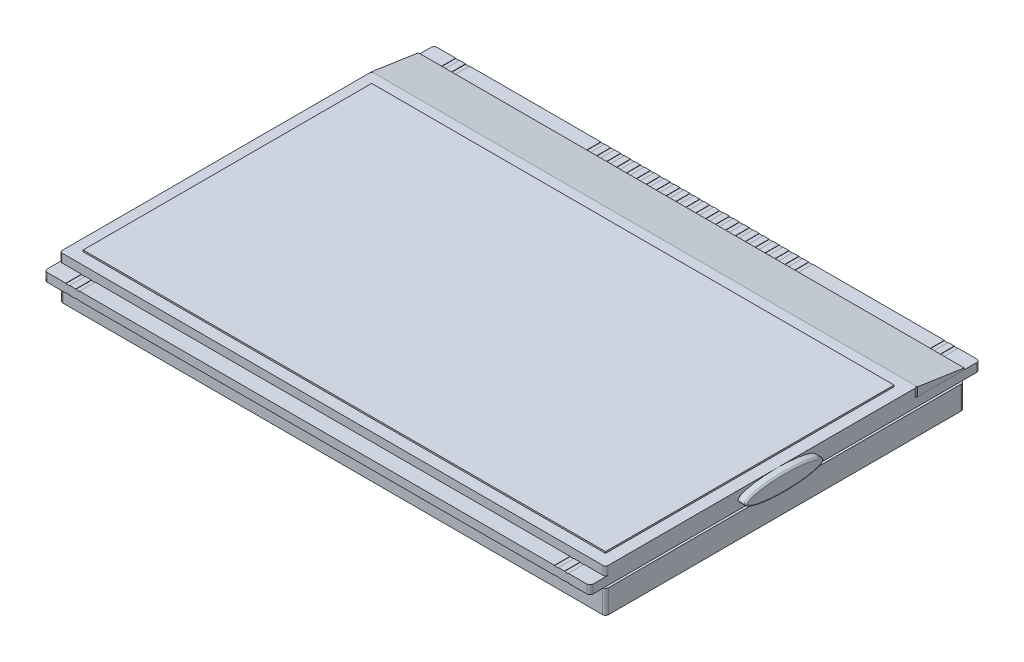
SolidWorks part; units mm, degrees
ref_plane "Front Plane" through (0, 0, 0) normal (0, 0, 1) x (1, 0, 0)
ref_plane "Top Plane" through (0, 0, 0) normal (0, 1, 0) x (1, 0, 0)
ref_plane "Right Plane" through (0, 0, 0) normal (1, 0, 0) x (0, 0, -1)
sketch "Sketch2" plane through (0, 0, 0) normal (0, 1, 0) x (1, 0, 0)
  line L0 (0, 27.3735) -> (0, -35) construction
  line L1 (-35, 27.0253) -> (35, 27.0253)
  line L2 (-35, 27.0253) -> (-35, -22.9747)
  line L3 (-35, -22.9747) -> (35, -22.9747)
  line L4 (35, 27.0253) -> (35, -22.9747)
  line L5 (-33.5, 17.5253) -> (33.5, 17.5253)
  line L6 (-33.5, 17.5253) -> (-33.5, -19.4747)
  line L7 (-33.5, -19.4747) -> (33.5, -19.4747)
  line L8 (33.5, 17.5253) -> (33.5, -19.4747)
  line L9 (-33.5, -19.4747) -> (33.5, -19.4747)
  line L10 (-35, -20.9747) -> (35, -20.9747)
  line L11 (-35, 19.0253) -> (35, 19.0253)
  point P0 (0, 0)
  point P6 (0, 0)
  dimension "D1" = 70
  dimension "D2" = 50
  dimension "D3" = 67
  dimension "D4" = 37
  dimension "D5" = 3.5
  dimension "D6" = 2
  dimension "D7" = 40
extrude "Boss-Extrude1" add sketch "Sketch2" along normal blind 1.1 contours L11 L0 L5 L8 L9 L10 L4 | L0 L11 L2 L10 L7 L6 L5 region at (17.5, 0, -18.4938) region at (-0.5315, 0, -18.2753)
extrude "Boss-Extrude2" add sketch "Sketch2<4>" along normal blind 1.3 separate body contours L0 L5 L6 L7 | L5 L0 L9 L8 region at (16.75, 0, 0.9747) region at (-16.75, 0, 0.9747)
sketch "Sketch2<4>" plane through (0, 0, 0) normal (0, 1, 0) x (1, 0, 0) same geometry as "Sketch2"
extrude "Boss-Extrude3" add sketch "Sketch2<5>" against normal blind 1.1 separate body contours L1 L0 L11 L4 | L0 L1 L2 L11 | L11 L0 L5 L8 L9 L10 L4 | L0 L11 L2 L10 L7 L6 L5 | L5 L0 L9 L8 | L0 L5 L6 L7 | L10 L0 L3 L4 | L0 L10 L2 L3 region at (17.5, 0, -23.0253) region at (-17.5, 0, -23.0253) region at (17.5, 0, -18.4938) region at (-0.5315, 0, -18.2753) region at (16.75, 0, 0.9747) region at (-16.75, 0, 0.9747) region at (-17.5, 0, 21.9747) region at (17.5, 0, 21.9747)
sketch "Sketch2<5>" plane through (0, 0, 0) normal (0, 1, 0) x (1, 0, 0) same geometry as "Sketch2"
sketch "Sketch4" plane through (0, -1.1, 0) normal (0, -1, 0) x (1, 0, 0)
  line L4 (33.5, 19.4747) -> (-33.5, 19.4747)
  line L5 (33.5, -17.5253) -> (33.5, 19.4747)
  line L6 (-33.5, -17.5253) -> (33.5, -17.5253)
  line L7 (-33.5, 19.4747) -> (-33.5, -17.5253)
  line L8 (33.5, 19.4747) -> (-33.5, 19.4747)
  line L9 (33.5, -17.5253) -> (33.5, 19.4747)
  line L10 (-33.5, -17.5253) -> (33.5, -17.5253)
  line L11 (-33.5, 19.4747) -> (-33.5, -17.5253)
  dimension "D1" = 0
extrude "Boss-Extrude4" add sketch "Sketch4" along normal blind 0.3
sketch "Sketch5" plane through (0, -1.4, 0) normal (0, -1, 0) x (1, 0, 0)
  line L0 (-45.4868, 20.9747) -> (47.8611, 20.9747) construction
  line L1 (-45.4868, -25.0253) -> (53.1096, -25.0253) construction
  line L2 (-35, -27.0253) -> (35, -27.0253) construction
  line L3 (-35, 22.9747) -> (35, 22.9747) construction
  line L4 (35, -19.0253) -> (35, -25.0253)
  line L5 (35, -25.0253) -> (-35, -25.0253)
  line L6 (-35, -25.0253) -> (-35, -19.0253)
  line L8 (-35, -19.0253) -> (35, -19.0253)
  line L9 (-35, 20.9747) -> (-35, -19.0253)
  line L10 (35, 20.9747) -> (-35, 20.9747)
  line L11 (35, -19.0253) -> (35, 20.9747)
  line L13 (-35, 20.9747) -> (-35, -19.0253)
  line L14 (35, 20.9747) -> (-35, 20.9747)
  line L15 (35, -19.0253) -> (35, 20.9747)
  dimension "D1" = 2
  dimension "D2" = 2
  dimension "D3" = 0
extrude "Boss-Extrude5" add sketch "Sketch5" along normal blind 3 separate body
fillet "Fillet1" radius 0.3 4 edges at (35, 0.55, 20.9747) (-35, 0.55, 20.9747) (-35, 0.55, -19.0253) (35, 0.55, -19.0253)
fillet "Fillet2" radius 0.4 4 edges at (35, -0.55, 22.9747) (35, -0.55, -27.0253) (-35, -0.55, -27.0253) (-35, -0.55, 22.9747)
fillet "Fillet3" radius 0.4 4 edges at (-35, -2.9, -25.0253) (35, -2.9, -25.0253) (35, -2.9, 20.9747) (-35, -2.9, 20.9747)
sketch "Sketch9" plane through (0, -4.4, 0) normal (0, -1, 0) x (1, 0, 0)
  line L0 (-34.6, -27.0253) -> (34.6, -27.0253) construction
  line L1 (25, -24.0253) -> (24, -24.0253)
  line L2 (25, -24.0253) -> (25, -23.4253)
  line L3 (25, -23.4253) -> (24, -23.4253)
  line L4 (24, -24.0253) -> (24, -23.4253)
  line L5 (25, -24.0253) -> (24, -23.4253) construction
  line L6 (25, -23.4253) -> (24, -24.0253) construction
  line L7 (-34.6, -27.0253) -> (34.6, -27.0253) construction
  line L8 (0, 0) -> (0, -35.522) construction
  line L9 (-25, -23.4253) -> (-24, -24.0253) construction
  line L10 (-25, -24.0253) -> (-24, -23.4253) construction
  line L11 (-24, -24.0253) -> (-24, -23.4253)
  line L12 (-25, -23.4253) -> (-24, -23.4253)
  line L13 (-25, -24.0253) -> (-25, -23.4253)
  line L14 (-25, -24.0253) -> (-24, -24.0253)
  point P0 (24.5, -23.7253)
  point P10 (0, -17.761)
  point P15 (-24.5, -23.7253)
  dimension "D1" = 1
  dimension "D2" = 0.6
  dimension "D3" = 3.3
  dimension "D4" = 24.5
extrude "Boss-Extrude6" add sketch "Sketch9" along normal blind 3 separate body
sketch "Sketch10" plane through (0, 0, 0) normal (0, 1, 0) x (1, 0, 0)
  line L0 (-34.7, -20.9747) -> (34.7, -20.9747) construction
  line L1 (-32.225, -20.9747) -> (-31.725, -20.9747)
  line L2 (-32.225, -20.9747) -> (-32.225, -23.4004)
  line L3 (-32.225, -23.4004) -> (-31.725, -23.4004)
  line L4 (-31.725, -20.9747) -> (-31.725, -23.4004)
  line L5 (-30.945, -20.9747) -> (-30.945, -23.4004)
  line L6 (-30.445, -20.9747) -> (-30.445, -23.4004)
  line L7 (-30.945, -20.9747) -> (-30.445, -20.9747)
  line L8 (-30.945, -23.4004) -> (-30.445, -23.4004)
  line L9 (-34.7, -20.9747) -> (-30.445, -20.9747) construction
  line L10 (-35, 26.6253) -> (-35, -22.5747) construction
  line L11 (0, -25.9549) -> (0, 4.9438) construction
  line L12 (30.445, -22.9747) -> (34.6, -22.9747)
  line L13 (30.945, -23.4004) -> (30.445, -23.4004)
  line L14 (30.945, -20.9747) -> (30.445, -20.9747)
  line L15 (30.445, -20.9747) -> (30.445, -23.4004)
  line L16 (30.945, -20.9747) -> (30.945, -23.4004)
  line L17 (31.725, -20.9747) -> (31.725, -23.4004)
  line L18 (32.225, -23.4004) -> (31.725, -23.4004)
  line L19 (32.225, -20.9747) -> (32.225, -23.4004)
  line L20 (32.225, -20.9747) -> (31.725, -20.9747)
  line L21 (-45.6387, 2.0253) -> (48.5913, 2.0253) construction
  line L22 (30.445, -20.9747) -> (34.7, -20.9747) construction
  line L23 (32.225, 25.0253) -> (31.725, 25.0253)
  line L24 (32.225, 25.0253) -> (32.225, 27.451)
  line L25 (-34.6, -22.9747) -> (34.6, -22.9747)
  line L26 (35, -22.5747) -> (35, 26.6253)
  line L27 (34.6, 27.0253) -> (-34.6, 27.0253)
  line L28 (-35, 26.6253) -> (-35, -22.5747)
  line L29 (-34.6, -22.9747) -> (-30.445, -22.9747)
  line L31 (32.225, 27.451) -> (31.725, 27.451)
  line L33 (31.725, 25.0253) -> (31.725, 27.451)
  line L34 (30.945, 25.0253) -> (30.945, 27.451)
  line L35 (30.445, 25.0253) -> (30.445, 27.451)
  line L36 (30.945, 25.0253) -> (30.445, 25.0253)
  line L37 (30.945, 27.451) -> (30.445, 27.451)
  line L38 (-30.945, 27.451) -> (-30.445, 27.451)
  line L39 (-30.945, 25.0253) -> (-30.445, 25.0253)
  line L40 (-30.445, 25.0253) -> (-30.445, 27.451)
  line L41 (-30.945, 25.0253) -> (-30.945, 27.451)
  line L42 (-31.725, 25.0253) -> (-31.725, 27.451)
  line L43 (-32.225, 27.451) -> (-31.725, 27.451)
  line L44 (-32.225, 25.0253) -> (-32.225, 27.451)
  line L45 (-32.225, 25.0253) -> (-31.725, 25.0253)
  arc A4 (34.6, -22.9747) -> (35, -22.5747) centre (34.6, -22.5747) ccw
  arc A5 (35, 26.6253) -> (34.6, 27.0253) centre (34.6, 26.6253) ccw
  arc A6 (-34.6, 27.0253) -> (-35, 26.6253) centre (-34.6, 26.6253) ccw
  arc A7 (-35, -22.5747) -> (-34.6, -22.9747) centre (-34.6, -22.5747) ccw
  arc A8 (34.6, -22.9747) -> (35, -22.5747) centre (34.6, -22.5747) ccw
  arc A9 (35, 26.6253) -> (34.6, 27.0253) centre (34.6, 26.6253) ccw
  arc A10 (-34.6, 27.0253) -> (-35, 26.6253) centre (-34.6, 26.6253) ccw
  arc A11 (-35, -22.5747) -> (-34.6, -22.9747) centre (-34.6, -22.5747) ccw
  point P4 (-31.975, -23.4004)
  line M6 (-34.6, -22.9747) -> (34.6, -22.9747)
  line M10 (34.6, 27.0253) -> (-34.6, 27.0253)
  dimension "D1" = 0.5
  dimension "D3" = 3.025
  dimension "D4" = 0
  dimension "D2" = 2
extrude "Cut-Extrude2" cut sketch "Sketch10" against normal blind 0.05 contours L19 L20 L17 M6 | L16 L14 L15 M6 | L41 L39 L40 M10 | L44 L45 L42 M10 | L33 L23 L24 M10 | L36 L34 L35 M10 | L5 L8 L6 L7 | L2 L3 L4 L1 region at (30.695, 0, 21.9747) region at (-31.975, 0, -26.0253) region at (31.975, 0, 21.9747) region at (-30.695, 0, -26.0253) region at (30.695, 0, -26.0253) region at (31.975, 0, -26.0253)
sketch "Sketch11" plane through (0, -1.1, 0) normal (0, -1, 0) x (1, 0, 0)
  line L0 (-32.225, 22.9747) -> (-31.725, 22.9747) construction
  line L1 (-31.725, 22.9747) -> (-31.725, 20.9747) construction
  line L2 (-31.725, 20.9747) -> (-32.225, 20.9747) construction
  line L3 (-32.225, 20.9747) -> (-32.225, 22.9747) construction
  line L4 (-30.945, 22.9747) -> (-30.445, 22.9747) construction
  line L5 (-30.445, 22.9747) -> (-30.445, 20.9747) construction
  line L6 (-30.445, 20.9747) -> (-30.945, 20.9747) construction
  line L7 (-30.945, 20.9747) -> (-30.945, 22.9747) construction
  line L8 (-32.225, 22.9747) -> (-31.725, 22.9747)
  line L9 (-31.725, 22.9747) -> (-31.725, 20.9747)
  line L10 (-31.725, 20.9747) -> (-32.225, 20.9747)
  line L11 (-32.225, 20.9747) -> (-32.225, 22.9747)
  line L12 (-30.945, 22.9747) -> (-30.445, 22.9747)
  line L13 (-30.445, 22.9747) -> (-30.445, 20.9747)
  line L14 (-30.445, 20.9747) -> (-30.945, 20.9747)
  line L15 (-30.945, 20.9747) -> (-30.945, 22.9747)
  line L16 (30.445, -25.0253) -> (30.945, -25.0253) construction
  line L17 (30.945, -25.0253) -> (30.945, -27.0253) construction
  line L18 (30.945, -27.0253) -> (30.445, -27.0253) construction
  line L19 (30.445, -27.0253) -> (30.445, -25.0253) construction
  line L20 (31.725, -27.0253) -> (31.725, -25.0253) construction
  line L21 (31.725, -25.0253) -> (32.225, -25.0253) construction
  line L22 (32.225, -25.0253) -> (32.225, -27.0253) construction
  line L23 (32.225, -27.0253) -> (31.725, -27.0253) construction
  line L24 (-30.945, -27.0253) -> (-30.945, -25.0253) construction
  line L25 (-30.945, -25.0253) -> (-30.445, -25.0253) construction
  line L26 (-30.445, -25.0253) -> (-30.445, -27.0253) construction
  line L27 (-30.445, -27.0253) -> (-30.945, -27.0253) construction
  line L28 (-32.225, -27.0253) -> (-32.225, -25.0253) construction
  line L29 (-32.225, -25.0253) -> (-31.725, -25.0253) construction
  line L30 (-31.725, -25.0253) -> (-31.725, -27.0253) construction
  line L31 (-31.725, -27.0253) -> (-32.225, -27.0253) construction
  line L32 (30.945, 22.9747) -> (30.945, 20.9747) construction
  line L33 (30.945, 20.9747) -> (30.445, 20.9747) construction
  line L34 (30.445, 20.9747) -> (30.445, 22.9747) construction
  line L35 (30.445, 22.9747) -> (30.945, 22.9747) construction
  line L36 (32.225, 22.9747) -> (32.225, 20.9747) construction
  line L37 (32.225, 20.9747) -> (31.725, 20.9747) construction
  line L38 (31.725, 20.9747) -> (31.725, 22.9747) construction
  line L39 (31.725, 22.9747) -> (32.225, 22.9747) construction
  line L40 (30.445, -25.0253) -> (30.945, -25.0253)
  line L41 (30.945, -25.0253) -> (30.945, -27.0253)
  line L42 (30.945, -27.0253) -> (30.445, -27.0253)
  line L43 (30.445, -27.0253) -> (30.445, -25.0253)
  line L44 (31.725, -27.0253) -> (31.725, -25.0253)
  line L45 (31.725, -25.0253) -> (32.225, -25.0253)
  line L46 (32.225, -25.0253) -> (32.225, -27.0253)
  line L47 (32.225, -27.0253) -> (31.725, -27.0253)
  line L48 (-30.945, -27.0253) -> (-30.945, -25.0253)
  line L49 (-30.945, -25.0253) -> (-30.445, -25.0253)
  line L50 (-30.445, -25.0253) -> (-30.445, -27.0253)
  line L51 (-30.445, -27.0253) -> (-30.945, -27.0253)
  line L52 (-32.225, -27.0253) -> (-32.225, -25.0253)
  line L53 (-32.225, -25.0253) -> (-31.725, -25.0253)
  line L54 (-31.725, -25.0253) -> (-31.725, -27.0253)
  line L55 (-31.725, -27.0253) -> (-32.225, -27.0253)
  line L56 (30.945, 22.9747) -> (30.945, 20.9747)
  line L57 (30.945, 20.9747) -> (30.445, 20.9747)
  line L58 (30.445, 20.9747) -> (30.445, 22.9747)
  line L59 (30.445, 22.9747) -> (30.945, 22.9747)
  line L60 (32.225, 22.9747) -> (32.225, 20.9747)
  line L61 (32.225, 20.9747) -> (31.725, 20.9747)
  line L62 (31.725, 20.9747) -> (31.725, 22.9747)
  line L63 (31.725, 22.9747) -> (32.225, 22.9747)
extrude "Cut-Extrude3" cut sketch "Sketch11" against normal blind 0.05
sketch "Sketch12" plane through (0, 0, 0) normal (0, 1, 0) x (1, 0, 0)
  line L0 (-30.445, 27.0253) -> (30.445, 27.0253) construction
  line L1 (13.555, 25.0253) -> (13.055, 25.0253)
  line L2 (13.555, 25.0253) -> (13.555, 27.0253)
  line L3 (13.555, 27.0253) -> (13.055, 27.0253)
  line L4 (13.055, 25.0253) -> (13.055, 27.0253)
  line L5 (30.945, 27.0253) -> (30.445, 27.0253) construction
  line L6 (11.785, 25.0253) -> (11.785, 27.0253)
  line L7 (12.285, 27.0253) -> (11.785, 27.0253)
  line L8 (12.285, 25.0253) -> (12.285, 27.0253)
  line L9 (12.285, 25.0253) -> (11.785, 25.0253)
  line L10 (10.515, 25.0253) -> (10.515, 27.0253)
  line L11 (11.015, 27.0253) -> (10.515, 27.0253)
  line L12 (11.015, 25.0253) -> (11.015, 27.0253)
  line L13 (11.015, 25.0253) -> (10.515, 25.0253)
  line L14 (9.245, 25.0253) -> (9.245, 27.0253)
  line L15 (9.745, 27.0253) -> (9.245, 27.0253)
  line L16 (9.745, 25.0253) -> (9.745, 27.0253)
  line L17 (9.745, 25.0253) -> (9.245, 25.0253)
  line L18 (7.975, 25.0253) -> (7.975, 27.0253)
  line L19 (8.475, 27.0253) -> (7.975, 27.0253)
  line L20 (8.475, 25.0253) -> (8.475, 27.0253)
  line L21 (8.475, 25.0253) -> (7.975, 25.0253)
  line L22 (6.705, 25.0253) -> (6.705, 27.0253)
  line L23 (7.205, 27.0253) -> (6.705, 27.0253)
  line L24 (7.205, 25.0253) -> (7.205, 27.0253)
  line L25 (7.205, 25.0253) -> (6.705, 25.0253)
  line L26 (5.435, 25.0253) -> (5.435, 27.0253)
  line L27 (5.935, 27.0253) -> (5.435, 27.0253)
  line L28 (5.935, 25.0253) -> (5.935, 27.0253)
  line L29 (5.935, 25.0253) -> (5.435, 25.0253)
  line L30 (4.165, 25.0253) -> (4.165, 27.0253)
  line L31 (4.665, 27.0253) -> (4.165, 27.0253)
  line L32 (4.665, 25.0253) -> (4.665, 27.0253)
  line L33 (4.665, 25.0253) -> (4.165, 25.0253)
  line L34 (2.895, 25.0253) -> (2.895, 27.0253)
  line L35 (3.395, 27.0253) -> (2.895, 27.0253)
  line L36 (3.395, 25.0253) -> (3.395, 27.0253)
  line L37 (3.395, 25.0253) -> (2.895, 25.0253)
  line L38 (1.625, 25.0253) -> (1.625, 27.0253)
  line L39 (2.125, 27.0253) -> (1.625, 27.0253)
  line L40 (2.125, 25.0253) -> (2.125, 27.0253)
  line L41 (2.125, 25.0253) -> (1.625, 25.0253)
  line L42 (0.355, 25.0253) -> (0.355, 27.0253)
  line L43 (0.855, 27.0253) -> (0.355, 27.0253)
  line L44 (0.855, 25.0253) -> (0.855, 27.0253)
  line L45 (0.855, 25.0253) -> (0.355, 25.0253)
  line L46 (-0.915, 25.0253) -> (-0.915, 27.0253)
  line L47 (-0.415, 27.0253) -> (-0.915, 27.0253)
  line L48 (-0.415, 25.0253) -> (-0.415, 27.0253)
  line L49 (-0.415, 25.0253) -> (-0.915, 25.0253)
  line L50 (-2.185, 25.0253) -> (-2.185, 27.0253)
  line L51 (-1.685, 27.0253) -> (-2.185, 27.0253)
  line L52 (-1.685, 25.0253) -> (-1.685, 27.0253)
  line L53 (-1.685, 25.0253) -> (-2.185, 25.0253)
  line L54 (-3.455, 25.0253) -> (-3.455, 27.0253)
  line L55 (-2.955, 27.0253) -> (-3.455, 27.0253)
  line L56 (-2.955, 25.0253) -> (-2.955, 27.0253)
  line L57 (-2.955, 25.0253) -> (-3.455, 25.0253)
  line L58 (-4.725, 25.0253) -> (-4.725, 27.0253)
  line L59 (-4.225, 27.0253) -> (-4.725, 27.0253)
  line L60 (-4.225, 25.0253) -> (-4.225, 27.0253)
  line L61 (-4.225, 25.0253) -> (-4.725, 25.0253)
  line L62 (-5.995, 25.0253) -> (-5.995, 27.0253)
  line L63 (-5.495, 27.0253) -> (-5.995, 27.0253)
  line L64 (-5.495, 25.0253) -> (-5.495, 27.0253)
  line L65 (-5.495, 25.0253) -> (-5.995, 25.0253)
  line L66 (-7.265, 25.0253) -> (-7.265, 27.0253)
  line L67 (-6.765, 27.0253) -> (-7.265, 27.0253)
  line L68 (-6.765, 25.0253) -> (-6.765, 27.0253)
  line L69 (-6.765, 25.0253) -> (-7.265, 25.0253)
  line L70 (-8.535, 25.0253) -> (-8.535, 27.0253)
  line L71 (-8.035, 27.0253) -> (-8.535, 27.0253)
  line L72 (-8.035, 25.0253) -> (-8.035, 27.0253)
  line L73 (-8.035, 25.0253) -> (-8.535, 25.0253)
  line L74 (-9.805, 25.0253) -> (-9.805, 27.0253)
  line L75 (-9.305, 27.0253) -> (-9.805, 27.0253)
  line L76 (-9.305, 25.0253) -> (-9.305, 27.0253)
  line L77 (-9.305, 25.0253) -> (-9.805, 25.0253)
  line L78 (-11.075, 25.0253) -> (-11.075, 27.0253)
  line L79 (-10.575, 27.0253) -> (-11.075, 27.0253)
  line L80 (-10.575, 25.0253) -> (-10.575, 27.0253)
  line L81 (-10.575, 25.0253) -> (-11.075, 25.0253)
  line L82 (-12.345, 25.0253) -> (-12.345, 27.0253)
  line L83 (-11.845, 27.0253) -> (-12.345, 27.0253)
  line L84 (-11.845, 25.0253) -> (-11.845, 27.0253)
  line L85 (-11.845, 25.0253) -> (-12.345, 25.0253)
  line L86 (-13.115, 25.0253) -> (-13.615, 25.0253)
  line L87 (-13.615, 25.0253) -> (-13.615, 27.0253)
  line L88 (-13.115, 27.0253) -> (-13.615, 27.0253)
  line L89 (-13.115, 25.0253) -> (-13.115, 27.0253)
  point P8 (30.695, 27.0253)
  point P9 (13.305, 27.0253)
  dimension "D1" = 0.5
  dimension "D2" = 17.39
  dimension "D3" = 21
  dimension "D4" = 2
extrude "Cut-Extrude4" cut sketch "Sketch12" against normal blind 0.05
sketch "Sketch13" plane through (0, -1.1, 0) normal (0, -1, 0) x (1, 0, 0)
  line L0 (-11.075, -25.0253) -> (-10.575, -25.0253) construction
  line L1 (-10.575, -25.0253) -> (-10.575, -27.0253) construction
  line L2 (-10.575, -27.0253) -> (-11.075, -27.0253) construction
  line L3 (-11.075, -27.0253) -> (-11.075, -25.0253) construction
  line L4 (-9.805, -25.0253) -> (-9.305, -25.0253) construction
  line L5 (-9.305, -25.0253) -> (-9.305, -27.0253) construction
  line L6 (-9.305, -27.0253) -> (-9.805, -27.0253) construction
  line L7 (-9.805, -27.0253) -> (-9.805, -25.0253) construction
  line L8 (-8.535, -25.0253) -> (-8.035, -25.0253) construction
  line L9 (-8.035, -25.0253) -> (-8.035, -27.0253) construction
  line L10 (-8.035, -27.0253) -> (-8.535, -27.0253) construction
  line L11 (-8.535, -27.0253) -> (-8.535, -25.0253) construction
  line L12 (-7.265, -25.0253) -> (-6.765, -25.0253) construction
  line L13 (-6.765, -25.0253) -> (-6.765, -27.0253) construction
  line L14 (-6.765, -27.0253) -> (-7.265, -27.0253) construction
  line L15 (-7.265, -27.0253) -> (-7.265, -25.0253) construction
  line L16 (-5.995, -25.0253) -> (-5.495, -25.0253) construction
  line L17 (-5.495, -25.0253) -> (-5.495, -27.0253) construction
  line L18 (-5.495, -27.0253) -> (-5.995, -27.0253) construction
  line L19 (-5.995, -27.0253) -> (-5.995, -25.0253) construction
  line L20 (-4.725, -25.0253) -> (-4.225, -25.0253) construction
  line L21 (-4.225, -25.0253) -> (-4.225, -27.0253) construction
  line L22 (-4.225, -27.0253) -> (-4.725, -27.0253) construction
  line L23 (-4.725, -27.0253) -> (-4.725, -25.0253) construction
  line L24 (-12.345, -25.0253) -> (-11.845, -25.0253) construction
  line L25 (-11.845, -25.0253) -> (-11.845, -27.0253) construction
  line L26 (-11.845, -27.0253) -> (-12.345, -27.0253) construction
  line L27 (-12.345, -27.0253) -> (-12.345, -25.0253) construction
  line L28 (1.625, -25.0253) -> (2.125, -25.0253) construction
  line L29 (2.125, -25.0253) -> (2.125, -27.0253) construction
  line L30 (2.125, -27.0253) -> (1.625, -27.0253) construction
  line L31 (1.625, -27.0253) -> (1.625, -25.0253) construction
  line L32 (2.895, -25.0253) -> (3.395, -25.0253) construction
  line L33 (3.395, -25.0253) -> (3.395, -27.0253) construction
  line L34 (3.395, -27.0253) -> (2.895, -27.0253) construction
  line L35 (2.895, -27.0253) -> (2.895, -25.0253) construction
  line L36 (4.165, -25.0253) -> (4.665, -25.0253) construction
  line L37 (4.665, -25.0253) -> (4.665, -27.0253) construction
  line L38 (4.665, -27.0253) -> (4.165, -27.0253) construction
  line L39 (4.165, -27.0253) -> (4.165, -25.0253) construction
  line L40 (5.435, -25.0253) -> (5.935, -25.0253) construction
  line L41 (5.935, -25.0253) -> (5.935, -27.0253) construction
  line L42 (5.935, -27.0253) -> (5.435, -27.0253) construction
  line L43 (5.435, -27.0253) -> (5.435, -25.0253) construction
  line L44 (6.705, -25.0253) -> (7.205, -25.0253) construction
  line L45 (7.205, -25.0253) -> (7.205, -27.0253) construction
  line L46 (7.205, -27.0253) -> (6.705, -27.0253) construction
  line L47 (6.705, -27.0253) -> (6.705, -25.0253) construction
  line L48 (0.355, -25.0253) -> (0.855, -25.0253) construction
  line L49 (0.855, -25.0253) -> (0.855, -27.0253) construction
  line L50 (0.855, -27.0253) -> (0.355, -27.0253) construction
  line L51 (0.355, -27.0253) -> (0.355, -25.0253) construction
  line L52 (-0.915, -25.0253) -> (-0.415, -25.0253) construction
  line L53 (-0.415, -25.0253) -> (-0.415, -27.0253) construction
  line L54 (-0.415, -27.0253) -> (-0.915, -27.0253) construction
  line L55 (-0.915, -27.0253) -> (-0.915, -25.0253) construction
  line L56 (-2.185, -25.0253) -> (-1.685, -25.0253) construction
  line L57 (-1.685, -25.0253) -> (-1.685, -27.0253) construction
  line L58 (-1.685, -27.0253) -> (-2.185, -27.0253) construction
  line L59 (-2.185, -27.0253) -> (-2.185, -25.0253) construction
  line L60 (-3.455, -25.0253) -> (-2.955, -25.0253) construction
  line L61 (-2.955, -25.0253) -> (-2.955, -27.0253) construction
  line L62 (-2.955, -27.0253) -> (-3.455, -27.0253) construction
  line L63 (-3.455, -27.0253) -> (-3.455, -25.0253) construction
  line L64 (7.975, -25.0253) -> (8.475, -25.0253) construction
  line L65 (8.475, -25.0253) -> (8.475, -27.0253) construction
  line L66 (8.475, -27.0253) -> (7.975, -27.0253) construction
  line L67 (7.975, -27.0253) -> (7.975, -25.0253) construction
  line L68 (9.245, -25.0253) -> (9.745, -25.0253) construction
  line L69 (9.745, -25.0253) -> (9.745, -27.0253) construction
  line L70 (9.745, -27.0253) -> (9.245, -27.0253) construction
  line L71 (9.245, -27.0253) -> (9.245, -25.0253) construction
  line L72 (10.515, -25.0253) -> (11.015, -25.0253) construction
  line L73 (11.015, -25.0253) -> (11.015, -27.0253) construction
  line L74 (11.015, -27.0253) -> (10.515, -27.0253) construction
  line L75 (10.515, -27.0253) -> (10.515, -25.0253) construction
  line L76 (11.785, -25.0253) -> (12.285, -25.0253) construction
  line L77 (12.285, -25.0253) -> (12.285, -27.0253) construction
  line L78 (12.285, -27.0253) -> (11.785, -27.0253) construction
  line L79 (11.785, -27.0253) -> (11.785, -25.0253) construction
  line L80 (13.555, -25.0253) -> (13.555, -27.0253) construction
  line L81 (13.555, -27.0253) -> (13.055, -27.0253) construction
  line L82 (13.055, -27.0253) -> (13.055, -25.0253) construction
  line L83 (13.055, -25.0253) -> (13.555, -25.0253) construction
  line L84 (-11.075, -25.0253) -> (-10.575, -25.0253)
  line L85 (-10.575, -25.0253) -> (-10.575, -27.0253)
  line L86 (-10.575, -27.0253) -> (-11.075, -27.0253)
  line L87 (-11.075, -27.0253) -> (-11.075, -25.0253)
  line L88 (-9.805, -25.0253) -> (-9.305, -25.0253)
  line L89 (-9.305, -25.0253) -> (-9.305, -27.0253)
  line L90 (-9.305, -27.0253) -> (-9.805, -27.0253)
  line L91 (-9.805, -27.0253) -> (-9.805, -25.0253)
  line L92 (-8.535, -25.0253) -> (-8.035, -25.0253)
  line L93 (-8.035, -25.0253) -> (-8.035, -27.0253)
  line L94 (-8.035, -27.0253) -> (-8.535, -27.0253)
  line L95 (-8.535, -27.0253) -> (-8.535, -25.0253)
  line L96 (-7.265, -25.0253) -> (-6.765, -25.0253)
  line L97 (-6.765, -25.0253) -> (-6.765, -27.0253)
  line L98 (-6.765, -27.0253) -> (-7.265, -27.0253)
  line L99 (-7.265, -27.0253) -> (-7.265, -25.0253)
  line L100 (-5.995, -25.0253) -> (-5.495, -25.0253)
  line L101 (-5.495, -25.0253) -> (-5.495, -27.0253)
  line L102 (-5.495, -27.0253) -> (-5.995, -27.0253)
  line L103 (-5.995, -27.0253) -> (-5.995, -25.0253)
  line L104 (-4.725, -25.0253) -> (-4.225, -25.0253)
  line L105 (-4.225, -25.0253) -> (-4.225, -27.0253)
  line L106 (-4.225, -27.0253) -> (-4.725, -27.0253)
  line L107 (-4.725, -27.0253) -> (-4.725, -25.0253)
  line L108 (-12.345, -25.0253) -> (-11.845, -25.0253)
  line L109 (-11.845, -25.0253) -> (-11.845, -27.0253)
  line L110 (-11.845, -27.0253) -> (-12.345, -27.0253)
  line L111 (-12.345, -27.0253) -> (-12.345, -25.0253)
  line L112 (1.625, -25.0253) -> (2.125, -25.0253)
  line L113 (2.125, -25.0253) -> (2.125, -27.0253)
  line L114 (2.125, -27.0253) -> (1.625, -27.0253)
  line L115 (1.625, -27.0253) -> (1.625, -25.0253)
  line L116 (2.895, -25.0253) -> (3.395, -25.0253)
  line L117 (3.395, -25.0253) -> (3.395, -27.0253)
  line L118 (3.395, -27.0253) -> (2.895, -27.0253)
  line L119 (2.895, -27.0253) -> (2.895, -25.0253)
  line L120 (4.165, -25.0253) -> (4.665, -25.0253)
  line L121 (4.665, -25.0253) -> (4.665, -27.0253)
  line L122 (4.665, -27.0253) -> (4.165, -27.0253)
  line L123 (4.165, -27.0253) -> (4.165, -25.0253)
  line L124 (5.435, -25.0253) -> (5.935, -25.0253)
  line L125 (5.935, -25.0253) -> (5.935, -27.0253)
  line L126 (5.935, -27.0253) -> (5.435, -27.0253)
  line L127 (5.435, -27.0253) -> (5.435, -25.0253)
  line L128 (6.705, -25.0253) -> (7.205, -25.0253)
  line L129 (7.205, -25.0253) -> (7.205, -27.0253)
  line L130 (7.205, -27.0253) -> (6.705, -27.0253)
  line L131 (6.705, -27.0253) -> (6.705, -25.0253)
  line L132 (0.355, -25.0253) -> (0.855, -25.0253)
  line L133 (0.855, -25.0253) -> (0.855, -27.0253)
  line L134 (0.855, -27.0253) -> (0.355, -27.0253)
  line L135 (0.355, -27.0253) -> (0.355, -25.0253)
  line L136 (-0.915, -25.0253) -> (-0.415, -25.0253)
  line L137 (-0.415, -25.0253) -> (-0.415, -27.0253)
  line L138 (-0.415, -27.0253) -> (-0.915, -27.0253)
  line L139 (-0.915, -27.0253) -> (-0.915, -25.0253)
  line L140 (-2.185, -25.0253) -> (-1.685, -25.0253)
  line L141 (-1.685, -25.0253) -> (-1.685, -27.0253)
  line L142 (-1.685, -27.0253) -> (-2.185, -27.0253)
  line L143 (-2.185, -27.0253) -> (-2.185, -25.0253)
  line L144 (-3.455, -25.0253) -> (-2.955, -25.0253)
  line L145 (-2.955, -25.0253) -> (-2.955, -27.0253)
  line L146 (-2.955, -27.0253) -> (-3.455, -27.0253)
  line L147 (-3.455, -27.0253) -> (-3.455, -25.0253)
  line L148 (7.975, -25.0253) -> (8.475, -25.0253)
  line L149 (8.475, -25.0253) -> (8.475, -27.0253)
  line L150 (8.475, -27.0253) -> (7.975, -27.0253)
  line L151 (7.975, -27.0253) -> (7.975, -25.0253)
  line L152 (9.245, -25.0253) -> (9.745, -25.0253)
  line L153 (9.745, -25.0253) -> (9.745, -27.0253)
  line L154 (9.745, -27.0253) -> (9.245, -27.0253)
  line L155 (9.245, -27.0253) -> (9.245, -25.0253)
  line L156 (10.515, -25.0253) -> (11.015, -25.0253)
  line L157 (11.015, -25.0253) -> (11.015, -27.0253)
  line L158 (11.015, -27.0253) -> (10.515, -27.0253)
  line L159 (10.515, -27.0253) -> (10.515, -25.0253)
  line L160 (11.785, -25.0253) -> (12.285, -25.0253)
  line L161 (12.285, -25.0253) -> (12.285, -27.0253)
  line L162 (12.285, -27.0253) -> (11.785, -27.0253)
  line L163 (11.785, -27.0253) -> (11.785, -25.0253)
  line L164 (13.555, -25.0253) -> (13.555, -27.0253)
  line L165 (13.555, -27.0253) -> (13.055, -27.0253)
  line L166 (13.055, -27.0253) -> (13.055, -25.0253)
  line L167 (13.055, -25.0253) -> (13.555, -25.0253)
  line L168 (-13.115, -27.0253) -> (-13.615, -27.0253)
  line L169 (-13.615, -27.0253) -> (-13.615, -25.0253)
  line L170 (-13.115, -25.0253) -> (-13.115, -27.0253)
  line L171 (-13.615, -25.0253) -> (-13.115, -25.0253)
  dimension "D1" = 2
extrude "Cut-Extrude5" cut sketch "Sketch13" against normal blind 0.05
sketch "Sketch15" plane through (35, 0, 0) normal (1, 0, 0) x (0, 0, -1)
  line L0 (18.7253, 0) -> (-20.6747, 0) construction
  line L1 (26.6253, 0) -> (-22.5747, 0) construction
  line L3 (-20.9747, 0) -> (-20.9747, 1.1) construction
  ellipse E0 centre (1.0253, 0) end of major axis (6.0253, 0) minor radius 1.1
  dimension "D1" = 5
  dimension "D2" = 17
extrude "Boss-Extrude7" add sketch "Sketch15" along normal blind 1
fillet "Fillet4" radius 0.2 1 edges at (36, 0, -6.0253)
sketch "Sketch16" plane through (35, 0, 0) normal (1, 0, 0) x (0, 0, -1)
  line L0 (25.0253, 0) -> (25.0253, 0.2)
  line L1 (19.0253, 0) -> (25.0253, 0)
  line L2 (19.0253, 0) -> (19.0253, 1.1)
  line L3 (19.0253, 1.1) -> (25.0253, 0.2)
  dimension "D1" = 0.2
extrude "Boss-Extrude8" add sketch "Sketch16" against normal blind 70 separate body
